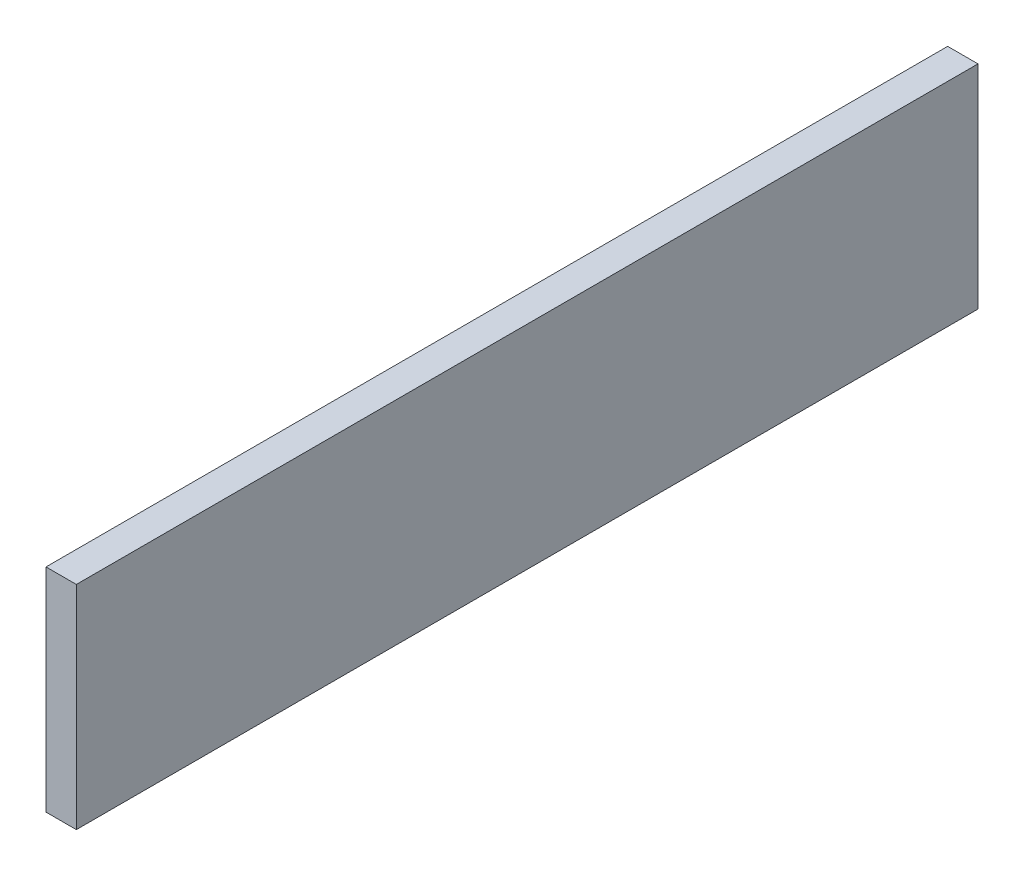
SolidWorks part; units mm, degrees
material "Hexcel AS4C (3000 Filaments)"
ref_plane "Front Plane" through (0, 0, 0) normal (0, 0, 1) x (1, 0, 0)
ref_plane "Top Plane" through (0, 0, 0) normal (0, 1, 0) x (1, 0, 0)
ref_plane "Right Plane" through (0, 0, 0) normal (1, 0, 0) x (0, 0, -1)
sketch "Sketch1" plane through (0, 0, 0) normal (0, 0, 1) x (1, 0, 0)
  line L0 (-2, -14) -> (2, -14)
  line L1 (-2, -14) -> (-2, 14)
  line L2 (2, -14) -> (2, 14)
  line L3 (-2, 14) -> (2, 14)
  line L4 (-2, -14) -> (2, 14) construction
  line L5 (2, -14) -> (-2, 14) construction
  point P1 (0, 0)
  dimension "D1" = 4
  dimension "D2" = 28
extrude "Boss-Extrude1" add sketch "Sketch1" along normal blind 59.44 and the other way blind 59.44
